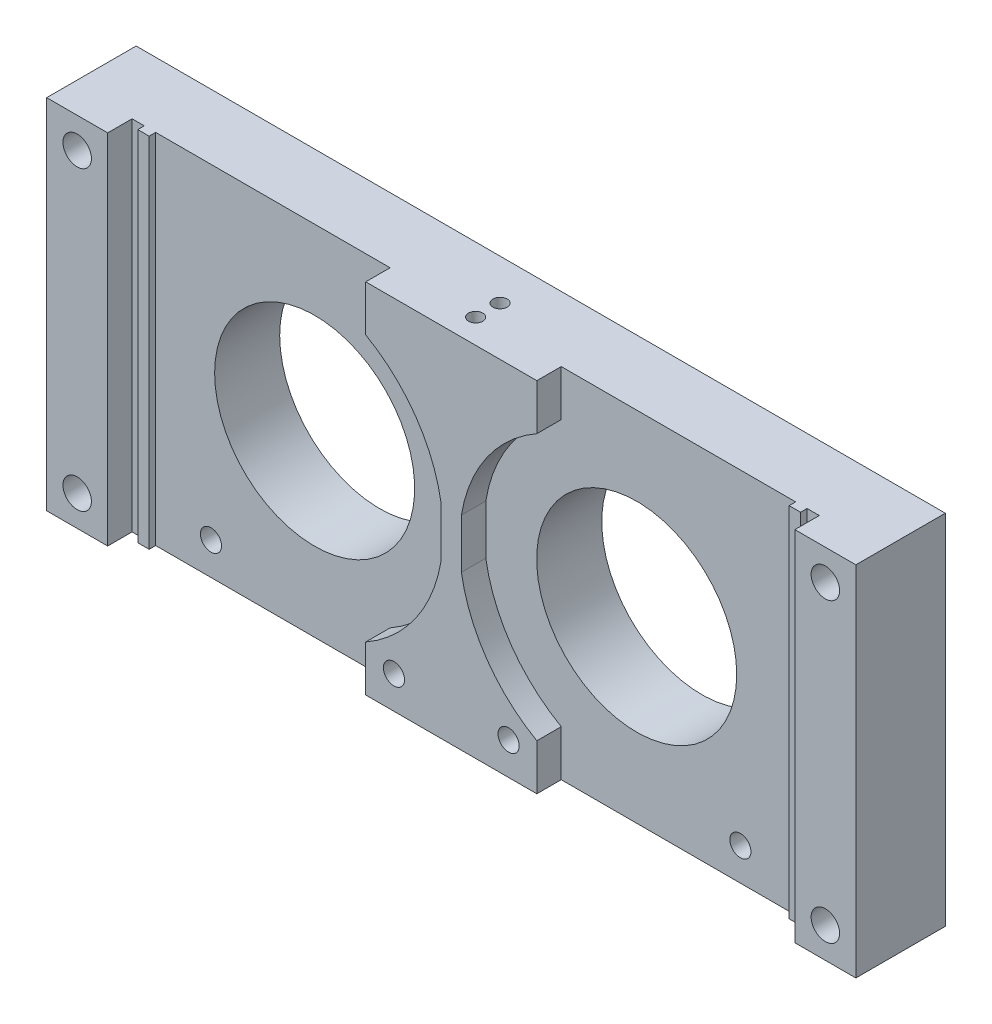
SolidWorks part; units mm, degrees
ref_plane "Front Plane" through (0, 0, 0) normal (0, 0, 1) x (1, 0, 0)
ref_plane "Top Plane" through (0, 0, 0) normal (0, 1, 0) x (1, 0, 0)
ref_plane "Right Plane" through (0, 0, 0) normal (1, 0, 0) x (0, 0, -1)
sketch "Sketch1" plane through (0, 0, 0) normal (0, 0, 1) x (1, 0, 0)
  line L0 (12.8092, 23.1231) -> (12.8092, -20.8769) construction
  line L1 (-36.9408, 23.1231) -> (62.5592, 23.1231)
  line L2 (-36.9408, 23.1231) -> (-36.9408, -20.8769)
  line L3 (-36.9408, -20.8769) -> (62.5592, -20.8769)
  line L4 (62.5592, 23.1231) -> (62.5592, -20.8769)
  circle A1 centre (-6.9908, 1.1231) radius 12.3
  circle A2 centre (32.6092, 1.1231) radius 12.3
  point P10 (12.8092, 1.1231)
  dimension "D3" = 22
  dimension "D2" = 19.8
  dimension "D4" = 24.6
  dimension "D1" = 99.5
  dimension "width" = 44
extrude "Boss-Extrude1" add sketch "Sketch1" along normal blind 6 contours L1 L4 L3 L2
sketch "Sketch2" plane through (0, 0, 6) normal (0, 0, 1) x (1, 0, 0)
  line L1 (-36.9408, 23.1231) -> (62.5592, 23.1231) construction
  line L3 (-36.9408, 23.1231) -> (-36.9408, -20.8769) construction
  line L4 (12.8092, 23.1231) -> (12.8092, -20.8769) construction
  line L5 (-36.9408, -20.8769) -> (62.5592, -20.8769) construction
  line L8 (-36.9408, 1.1231) -> (62.5592, 1.1231) construction
  line L9 (62.5592, 23.1231) -> (62.5592, -20.8769) construction
  line L15 (-36.9408, 23.1231) -> (-29.4408, 23.1231)
  line L16 (-36.9408, 23.1231) -> (-36.9408, -20.8769)
  line L17 (-36.9408, -20.8769) -> (-29.4408, -20.8769)
  line L18 (-29.4408, 23.1231) -> (-29.4408, -20.8769)
  line L19 (62.5592, 23.1231) -> (55.0592, 23.1231)
  line L20 (62.5592, 23.1231) -> (62.5592, -20.8769)
  line L21 (62.5592, -20.8769) -> (55.0592, -20.8769)
  line L22 (55.0592, 23.1231) -> (55.0592, -20.8769)
  circle A1 centre (-33.1908, 19.3731) radius 1.75
  circle A2 centre (58.8092, 19.3731) radius 1.75
  circle A4 centre (58.8092, -17.1269) radius 1.75
  circle A6 centre (-33.1908, -17.1269) radius 1.75
  dimension "D1" = 7.5
  dimension "D2" = 3.5
  dimension "D4" = 92
  dimension "D3" = 36.5
  dimension "D5" = 7.5
sketch "Sketch5" plane through (0, 0, 0) normal (0, 0, -1) x (-1, 0, 0)
  line L0 (36.9408, 23.1231) -> (-62.5592, 23.1231) construction
  line L1 (-12.8092, 23.1231) -> (-12.8092, -20.8769) construction
  line L2 (36.9408, -20.8769) -> (-62.5592, -20.8769) construction
  circle A1 centre (6.9908, 1.1231) radius 12.3
  circle A2 centre (-32.6092, 1.1231) radius 12.3
  dimension "D2" = 24.6
  dimension "D3" = 19.8
  dimension "D4" = 22
extrude "Cut-Extrude1" cut sketch "Sketch5" against normal blind 6 contours A2
extrude "Cut-Extrude4" cut sketch "Sketch5<5>" against normal blind 6
sketch "Sketch5<5>" plane through (0, 0, 0) normal (0, 0, -1) x (-1, 0, 0) same geometry as "Sketch5"
extrude "Cut-Extrude8" cut sketch "Sketch2" against normal blind 6 contours A1 | A6 | A2 | A4
extrude "Boss-Extrude5" add sketch "Sketch2<15>" along normal blind 3
sketch "Sketch2<15>" plane through (0, 0, 6) normal (0, 0, 1) x (1, 0, 0) same geometry as "Sketch2"
sketch "Sketch6" plane through (0, 0, 6) normal (0, 0, 1) x (1, 0, 0)
  line L0 (-29.4408, -20.8769) -> (55.0592, -20.8769) construction
  line L1 (11.5592, -20.8769) -> (14.0592, -20.8769)
  line L2 (11.5601, -1.9269) -> (11.5601, 4.1731)
  line L3 (11.5592, 23.1231) -> (14.0592, 23.1231)
  line L4 (14.0582, -1.9269) -> (14.0582, 4.1731)
  line L5 (-29.4408, 23.1231) -> (55.0592, 23.1231) construction
  line L7 (2.2891, 23.1231) -> (11.5592, 23.1231)
  line L9 (2.2891, -20.8769) -> (11.5592, -20.8769)
  line L15 (23.3292, 23.1231) -> (14.0592, 23.1231)
  line L17 (23.3292, -20.8769) -> (14.0592, -20.8769)
  line L18 (2.2891, 23.1231) -> (2.2891, 17.4731)
  line L19 (2.2891, -20.8769) -> (2.2891, -15.2269)
  line L20 (23.3292, 23.1231) -> (23.3292, 17.4731)
  line L21 (23.3292, -20.8769) -> (23.3292, -15.2269)
  arc A1 (11.5601, 4.1731) -> (2.2891, 17.4731) centre (-6.9908, 1.1231) ccw
  circle A2 centre (-6.9908, 1.1231) radius 18.8
  arc A3 (2.2891, -15.2269) -> (11.5601, -1.9269) centre (-6.9908, 1.1231) ccw
  arc A5 (14.0582, -1.9269) -> (23.3292, -15.2269) centre (32.6092, 1.1231) ccw
  circle A6 centre (32.6092, 1.1231) radius 18.8
  arc A7 (23.3292, 17.4731) -> (14.0582, 4.1731) centre (32.6092, 1.1231) ccw
  point P8 (12.8092, -20.8769)
  dimension "D1" = 2.5
  dimension "D2" = 42.25
  dimension "D3" = 6.5
  dimension "D4" = 6.5
  dimension "D5" = 5.65
  dimension "D6" = 5.65
  dimension "D7" = 6.1
  dimension "D8" = 6.1
extrude "Boss-Extrude6" add sketch "Sketch6" along normal blind 3 contours L7 L3 L15 L20 A7 L4 A5 L21 L17 L1 L9 L19 A3 L2 A1 L18
sketch "Sketch8" plane through (0, 0, 6) normal (0, 0, 1) x (1, 0, 0)
  line L0 (-29.4408, 23.1231) -> (2.2891, 23.1231) construction
  line L1 (-27.9408, 23.1231) -> (-26.5408, 23.1231)
  line L2 (-27.9408, 23.1231) -> (-27.9408, -20.8769)
  line L3 (-27.9408, -20.8769) -> (-26.5408, -20.8769)
  line L4 (-26.5408, 23.1231) -> (-26.5408, -20.8769)
  line L5 (-29.4408, -20.8769) -> (2.2891, -20.8769) construction
  line L6 (-29.4408, -20.8769) -> (-29.4408, 23.1231) construction
  dimension "D1" = 1.4
  dimension "D2" = 1.5
extrude "Boss-Extrude7" add sketch "Sketch8" along normal blind 0.8
other "Move Face3" face at (60.5592, -17.1269, 0) offset 2 parameters "D1"=2
sketch "Sketch9" plane through (0, 0, 6) normal (0, 0, 1) x (1, 0, 0)
  line L0 (23.3292, 23.1231) -> (55.0592, 23.1231) construction
  line L1 (53.5592, 23.1231) -> (52.1592, 23.1231)
  line L2 (53.5592, 23.1231) -> (53.5592, -20.8769)
  line L3 (53.5592, -20.8769) -> (52.1592, -20.8769)
  line L4 (52.1592, 23.1231) -> (52.1592, -20.8769)
  line L5 (23.3292, -20.8769) -> (55.0592, -20.8769) construction
  line L6 (55.0592, 23.1231) -> (55.0592, -20.8769) construction
  dimension "D1" = 1.4
  dimension "D2" = 1.5
extrude "Boss-Extrude8" add sketch "Sketch9" along normal blind 0.8
sketch "Sketch12" plane through (0, 23.1231, 0) normal (0, 1, 0) x (1, 0, 0)
  line L0 (-36.9408, -9) -> (-36.9408, 2) construction
  line L2 (-36.9408, 2) -> (62.5592, 2) construction
  circle A0 centre (12.8092, -3) radius 0.875
  circle A2 centre (12.8092, -6) radius 0.875
  dimension "D1" = 1.75
  dimension "D2" = 1.75
  dimension "D6" = 49.75
  dimension "D3" = 49.75
  dimension "D4" = 5
  dimension "D5" = 3
extrude "Cut-Extrude13" cut sketch "Sketch12" against normal blind 44
sketch "Sketch14" plane through (0, 0, -2) normal (0, 0, -1) x (-1, 0, 0)
  line L0 (-62.5592, 23.1231) -> (-62.5592, -20.8769) construction
  line L1 (36.9408, 23.1231) -> (-62.5592, 23.1231) construction
  circle A0 centre (-12.8092, 18.1231) radius 1.3
  circle A1 centre (-12.8092, 12.1231) radius 1.3
  dimension "D1" = 49.75
  dimension "D7" = 2.6
  dimension "D8" = 2.6
  dimension "D2" = 5
  dimension "D3" = 6
  dimension "D4" = 49.75
extrude "Cut-Extrude15" cut sketch "Sketch14" against normal blind 6.5 contours A1 | A0
sketch "Sketch15" plane through (0, 0, -2) normal (0, 0, -1) x (-1, 0, 0)
  circle A0 centre (-12.8092, 18.1231) radius 1.6
  circle A1 centre (-12.8092, 12.1231) radius 1.6
  dimension "D1" = 3.2
  dimension "D2" = 3.2
extrude "Cut-Extrude17" cut sketch "Sketch15" against normal blind 4
sketch "Sketch17" plane through (0, 0, -2) normal (0, 0, -1) x (-1, 0, 0)
  line L0 (-62.5592, 23.1231) -> (-62.5592, -20.8769) construction
  line L1 (36.9408, 23.1231) -> (-62.5592, 23.1231) construction
  circle A0 centre (-12.8092, 4.1231) radius 1.3
  circle A1 centre (-12.8092, -1.8769) radius 1.3
  dimension "D1" = 2.6
  dimension "D2" = 2.6
  dimension "D3" = 49.75
  dimension "D4" = 49.75
  dimension "D5" = 19
  dimension "D6" = 6
extrude "Cut-Extrude18" cut sketch "Sketch17" against normal blind 5.8
sketch "Sketch18" plane through (0, 0, -2) normal (0, 0, -1) x (-1, 0, 0)
  circle A0 centre (-12.8092, 4.1231) radius 1.6
  circle A1 centre (-12.8092, -1.8769) radius 1.6
  dimension "D1" = 3.2
  dimension "D2" = 3.2
extrude "Cut-Extrude19" cut sketch "Sketch18" against normal blind 4
sketch "Sketch19" plane through (0, 0, -2) normal (0, 0, -1) x (-1, 0, 0)
  line L2 (-32.6092, 1.1231) -> (-32.6092, -20.8769) construction
  line L3 (36.9408, -20.8769) -> (-62.5592, -20.8769) construction
  line L4 (6.9908, 1.1231) -> (6.9908, -20.8769) construction
  circle A0 centre (-45.3592, -16.8769) radius 1.3
  circle A1 centre (-19.8592, -16.8769) radius 1.3
  circle A2 centre (-5.7592, -16.8769) radius 1.3
  circle A3 centre (19.7408, -16.8769) radius 1.3
  circle A4 centre (-32.6092, 1.1231) radius 12.3 construction
  circle A5 centre (6.9908, 1.1231) radius 12.3 construction
  dimension "D1" = 18
  dimension "D5" = 2.6
  dimension "D6" = 2.6
  dimension "D11" = 2.6
  dimension "D12" = 2.6
  dimension "D2" = 12.75
  dimension "D3" = 25.5
  dimension "D4" = 18
  dimension "D7" = 18
  dimension "D8" = 18
  dimension "D9" = 12.75
  dimension "D10" = 25.5
hole_wizard "CBORE for M5 Hex Head Bolt1" positions "3DSketch2" profile "Sketch20" counterbore size "M5" standard "ANSI Metric" end condition through all
sketch3d "3DSketch2"
  point P0 (45.3592, -16.8769, -2)
  point P3 (19.8592, -16.8769, -2)
  point P6 (5.7592, -16.8769, -2)
  point P9 (-19.7408, -16.8769, -2)
sketch "Sketch20" plane through (45.3592, -16.8769, -2) normal (1, 0, 0) x (0, 1, 0)
  line L0 (0, 0) -> (0, 11)
  line L1 (0, 11) -> (1.3, 11)
  line L3 (1.3, 11) -> (1.3, 4)
  line L4 (1.3, 4) -> (1.6, 4)
  line L5 (1.6, 4) -> (1.6, 0)
  line L7 (1.6, 0) -> (0, 0)
  line L11 (0, -6.35) -> (0, 107.95) construction
  dimension "Thru Hole Dia." = 2.6
  dimension "Thru Hole Depth" = 11
  dimension "C'Bore Dia." = 3.2
  dimension "C'Bore Depth" = 4
